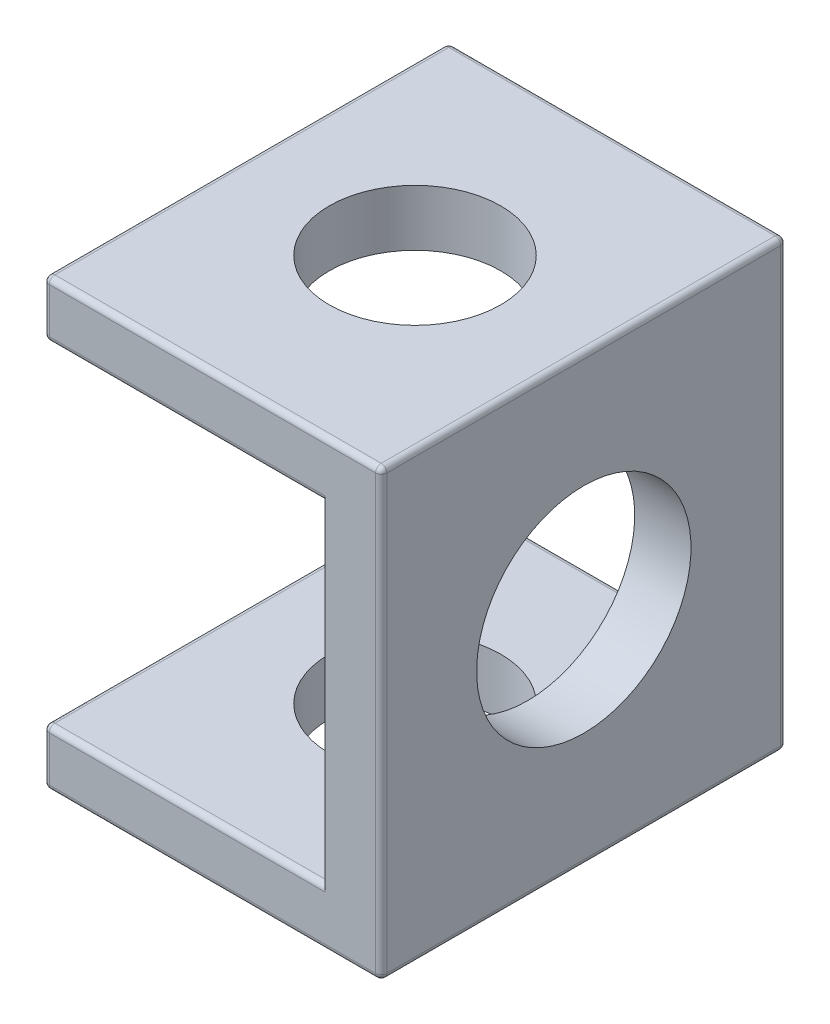
SolidWorks part; units mm, degrees
ref_plane "Front Plane" through (0, 0, 0) normal (0, 0, 1) x (1, 0, 0)
ref_plane "Top Plane" through (0, 0, 0) normal (0, 1, 0) x (1, 0, 0)
ref_plane "Right Plane" through (0, 0, 0) normal (1, 0, 0) x (0, 0, -1)
sketch "Sketch1" plane through (0, 0, 0) normal (0, 0, 1) x (1, 0, 0)
  line L0 (0, 0) -> (60, 0)
  line L1 (60, 0) -> (60, -79)
  line L2 (60, -79) -> (0, -79)
extrude "Extrude-Thin1" add sketch "Sketch1" along normal blind 72 thin thin type one direction wall 10
sketch "Sketch2" plane through (0, 0, 0) normal (0, 1, 0) x (1, 0, 0)
  circle A1 centre (30, -36) radius 15.24
extrude "Cut-Extrude2" cut sketch "Sketch2" against normal blind 10
sketch "Sketch3" plane through (0, -79, 0) normal (0, -1, 0) x (1, 0, 0)
  circle A0 centre (30, 36) radius 15.24
extrude "Cut-Extrude3" cut sketch "Sketch3" against normal blind 10
sketch "Sketch6" plane through (50, 0, 0) normal (-1, 0, 0) x (0, 0, 1)
  circle A0 centre (36, -39.5) radius 19.05
  point P11 (36, -39.5)
extrude "Cut-Extrude4" cut sketch "Sketch6" against normal blind 10
fillet "Fillet2" radius 1 2 edges at (0, 0, 36) (30, 0, 0)
fillet "Fillet3" radius 1 1 edges at (0, -10, 36)
fillet "Fillet4" radius 1 4 edges at (25.5, -10, 0) (0.2929, -9.7071, 0) (0.2929, -0.2929, 0.2929) (0, -5, 0)
fillet "Fillet5" radius 1 5 edges at (25.5, -10, 72) (0.2929, -9.7071, 72) (30.5, 0, 72) (0.2929, -0.2929, 72) (0, -5, 72)
fillet "Fillet6" radius 1 5 edges at (60, -40, 72) (60, -0.2929, 71.7071) (60, -40, 0) (60, -0.2929, 0.2929) (60, 0, 36)
fillet "Fillet7" radius 1 1 edges at (0, -69, 36)
fillet "Fillet8" radius 1 1 edges at (0, -79, 36)
fillet "Fillet9" radius 1 13 edges at (25.5, -69, 0) (0.2929, -69.2929, 0) (0, -74, 0) (0.2929, -78.7071, 0) (30, -79, 0) (59.7071, -79, 0.2929) (60, -79, 36) (59.7071, -79, 71.7071) (30, -79, 72) (0.2929, -78.7071, 72) (25.5, -69, 72) (0.2929, -69.2929, 72) (0, -74, 72)
